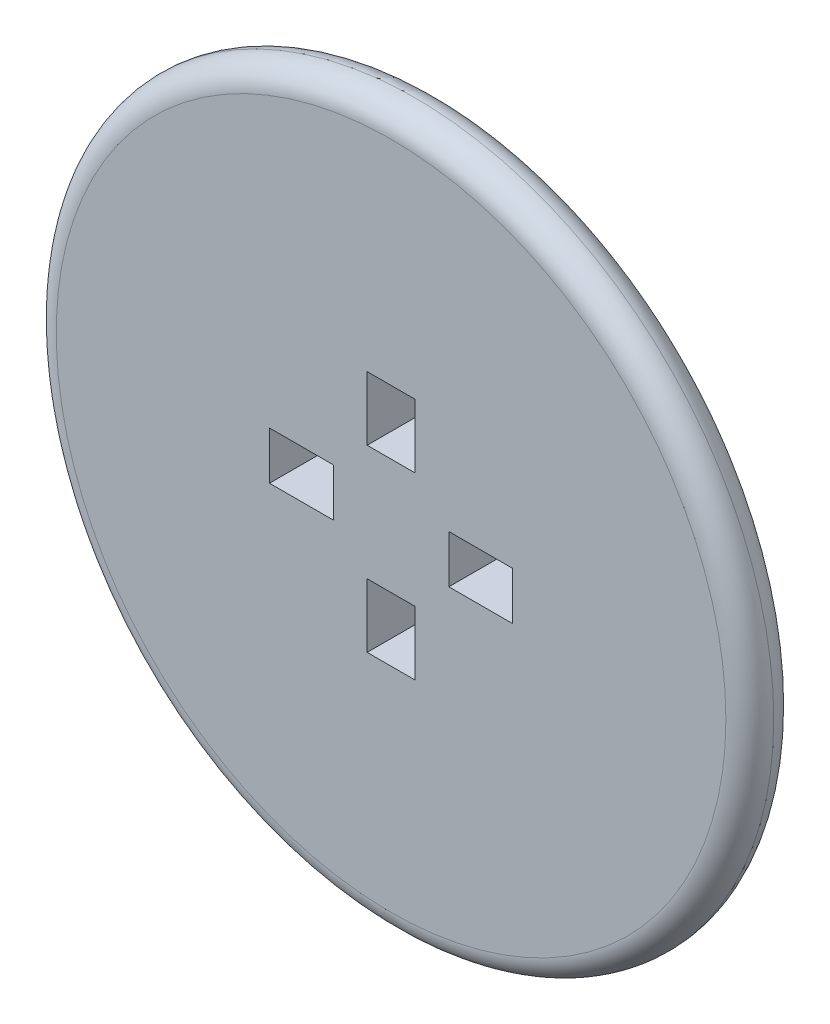
SolidWorks part; units mm, degrees
ref_plane "Front Plane" through (0, 0, 0) normal (0, 0, 1) x (1, 0, 0)
ref_plane "Top Plane" through (0, 0, 0) normal (0, 1, 0) x (1, 0, 0)
ref_plane "Right Plane" through (0, 0, 0) normal (1, 0, 0) x (0, 0, -1)
sketch "Sketch1" plane through (0, 0, 0) normal (0, 0, 1) x (1, 0, 0)
  line L0 (70.6211, 0) -> (-78.3667, 0) construction
  line L1 (0, 63.6729) -> (0, -48.4097) construction
  line L2 (11.25, 6.4926) -> (11.25, -7.8594) construction
  line L3 (-11.25, 13.2502) -> (-11.25, -1.1019) construction
  line L4 (10.0236, -11.25) -> (-13.213, -11.25) construction
  line L5 (26.6008, 11.25) -> (4.7311, 11.25) construction
  line L7 (7.25, 3) -> (15.25, 3)
  line L8 (7.25, 3) -> (7.25, -3)
  line L9 (7.25, -3) -> (15.25, -3)
  line L10 (15.25, 3) -> (15.25, -3)
  line L11 (7.25, 3) -> (15.25, -3) construction
  line L12 (7.25, -3) -> (15.25, 3) construction
  line L13 (-3, -15.25) -> (3, -15.25)
  line L14 (-15.25, -3) -> (-7.25, -3)
  line L15 (-15.25, -3) -> (-15.25, 3)
  line L16 (-15.25, 3) -> (-7.25, 3)
  line L17 (-7.25, -3) -> (-7.25, 3)
  line L18 (-15.25, -3) -> (-7.25, 3) construction
  line L19 (-15.25, 3) -> (-7.25, -3) construction
  line L20 (-3, -15.25) -> (-3, -7.25)
  line L21 (-3, -7.25) -> (3, -7.25)
  line L22 (3, -15.25) -> (3, -7.25)
  line L23 (-3, -15.25) -> (3, -7.25) construction
  line L24 (-3, -7.25) -> (3, -15.25) construction
  line L25 (-3, 7.25) -> (3, 7.25)
  line L26 (-3, 7.25) -> (-3, 15.25)
  line L27 (-3, 15.25) -> (3, 15.25)
  line L28 (3, 7.25) -> (3, 15.25)
  line L29 (-3, 7.25) -> (3, 15.25) construction
  line L30 (-3, 15.25) -> (3, 7.25) construction
  circle A0 centre (0, 0) radius 45
  point P15 (11.25, 0)
  point P20 (0, -11.25)
  point P21 (-11.25, 0)
  point P30 (0, 11.25)
  dimension "D1" = 90
  dimension "D2" = 4
  dimension "D3" = 4
  dimension "D4" = 4
  dimension "D5" = 4
  dimension "D6" = 11.25
  dimension "D7" = 11.25
  dimension "D8" = 11.25
  dimension "D9" = 11.25
  dimension "D10" = 6
  dimension "D11" = 6
  dimension "D12" = 6
  dimension "D13" = 6
extrude "Boss-Extrude1" add sketch "Sketch1" along normal blind 6
fillet "Fillet1" radius 3 1 edges at (45, 0, 6)
fillet "Fillet2" radius 3 1 edges at (45, 0, 0)
